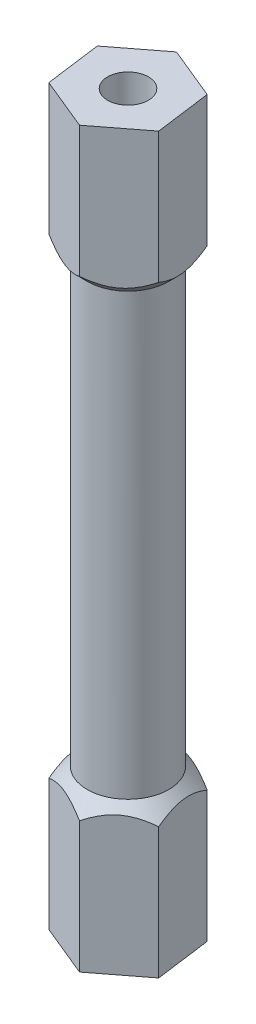
SolidWorks part; units mm, degrees
material "7050-T73510"
ref_plane "前视基准面" through (0, 0, 0) normal (0, 0, 1) x (1, 0, 0)
ref_plane "上视基准面" through (0, 0, 0) normal (0, 1, 0) x (1, 0, 0)
ref_plane "右视基准面" through (0, 0, 0) normal (1, 0, 0) x (0, 0, -1)
sketch "草图1" plane through (0, 0, 0) normal (0, 1, 0) x (1, 0, 0)
  circle A0 centre (0, 0) radius 2.5
  dimension "D1" = 5
extrude "凸台-拉伸1" add sketch "草图1" along normal blind 45
sketch "草图2" plane through (0, 45, 0) normal (0, 1, 0) x (1, 0, 0)
  line L1 (3.2029, -1.3196) -> (2.7443, 2.114)
  line L2 (2.7443, 2.114) -> (-0.4586, 3.4336)
  line L3 (-0.4586, 3.4336) -> (-3.2029, 1.3196)
  line L4 (-3.2029, 1.3196) -> (-2.7443, -2.114)
  line L5 (-2.7443, -2.114) -> (0.4586, -3.4336)
  line L6 (0.4586, -3.4336) -> (3.2029, -1.3196)
  circle A0 centre (0, 0) radius 3 construction
  dimension "D1" = 6
extrude "凸台-拉伸2" add sketch "草图2" against normal blind 8
sketch "草图3" plane through (0, 0, 0) normal (0, -1, 0) x (1, 0, 0)
  line L6 (3.2029, 1.3196) -> (0.4586, 3.4336)
  line L7 (0.4586, 3.4336) -> (-2.7443, 2.114)
  line L8 (-2.7443, 2.114) -> (-3.2029, -1.3196)
  line L9 (-3.2029, -1.3196) -> (-0.4586, -3.4336)
  line L10 (-0.4586, -3.4336) -> (2.7443, -2.114)
  line L11 (2.7443, -2.114) -> (3.2029, 1.3196)
  line L12 (3.2029, 1.3196) -> (0.4586, 3.4336)
  line L13 (0.4586, 3.4336) -> (-2.7443, 2.114)
  line L14 (-2.7443, 2.114) -> (-3.2029, -1.3196)
  line L15 (-3.2029, -1.3196) -> (-0.4586, -3.4336)
  line L16 (-0.4586, -3.4336) -> (2.7443, -2.114)
  line L17 (2.7443, -2.114) -> (3.2029, 1.3196)
  dimension "D1" = 0
extrude "凸台-拉伸3" add sketch "草图3" against normal blind 8
chamfer "倒角1" distance 1 angle 45 2 edges at (0, 8, -2.5) (0, 37, 2.5)
sketch "草图4" plane through (0, 0, 0) normal (0, 1, 0) x (-1, 0, 0)
  circle A0 centre (0, 0) radius 1.25
  dimension "D1" = 2.5
extrude "切除-拉伸1" cut sketch "草图4" along normal blind 8
cosmetic thread "装饰螺纹线2" parameters "D2"=3
sketch "草图5" plane through (0, 45, 0) normal (0, -1, 0) x (-1, 0, 0)
  circle A0 centre (0, 0) radius 1.25
  dimension "D1" = 2.5
extrude "切除-拉伸2" cut sketch "草图5" along normal blind 8
cosmetic thread "装饰螺纹线1" parameters "D2"=3
